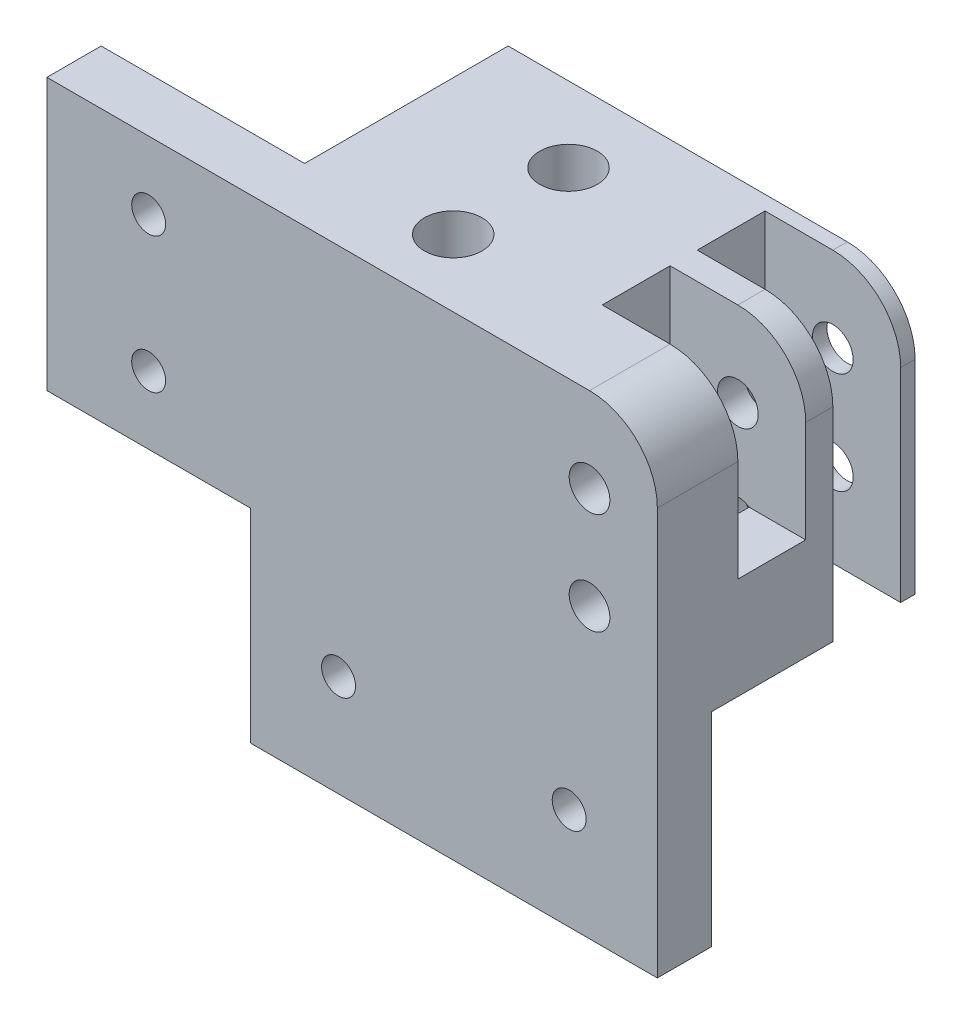
SolidWorks part; units mm, degrees
ref_plane "Front Plane" through (0, 0, 0) normal (0, 0, 1) x (1, 0, 0)
ref_plane "Top Plane" through (0, 0, 0) normal (0, 1, 0) x (1, 0, 0)
ref_plane "Right Plane" through (0, 0, 0) normal (1, 0, 0) x (0, 0, -1)
sketch "Esboço1" plane through (0, 0, 0) normal (0, 0, 1) x (1, 0, 0)
  line L0 (440, 72.2122) -> (440, 102.2122) construction
  line L1 (440, 72.2122) -> (380, 72.2122)
  line L2 (470, 102.2122) -> (470, 142.2122)
  line L3 (470, 142.2122) -> (390, 142.2122)
  line L4 (380, 72.2122) -> (380, 132.2122)
  line L5 (440, 102.2122) -> (470, 102.2122) construction
  line L6 (440, 72.2122) -> (440, 102.2122)
  line L7 (440, 102.2122) -> (470, 102.2122)
  line L9 (440, 87.2122) -> (380, 87.2122) construction
  line L10 (455, 102.2122) -> (455, 142.2122) construction
  arc A0 (390, 142.2122) -> (380, 132.2122) centre (390, 132.2122) ccw
  dimension "D1" = 10
  dimension "D2" = 40
  dimension "D3" = 60
extrude "Ressalto-extrusão1" add sketch "Esboço1" along normal blind 8 contours L4 A0 L3 L2 L7 L6 L1
hole_wizard "Broca de rosquear para tarraxa de M6x1.01" positions "Esboço2" profile "Esboço3" hole size "M6x1.0" standard "Ansi Metric" end condition through all
sketch "Esboço2" plane through (0, 0, 8) normal (0, 0, 1) x (1, 0, 0)
  line L0 (440, 87.2122) -> (380, 87.2122) construction
  line L1 (455, 102.2122) -> (455, 142.2122) construction
  line L2 (380, 72.2122) -> (380, 132.2122) construction
  line L3 (440, 72.2122) -> (440, 102.2122) construction
  line L4 (470, 142.2122) -> (390, 142.2122) construction
  point P0 (393, 87.2122)
  point P4 (427, 87.2122)
  point P6 (455, 112.2122)
  point P10 (455, 132.2122)
  dimension "D1" = 13
  dimension "D2" = 13
  dimension "D3" = 10
  dimension "D4" = 10
sketch "Esboço3" plane through (393, 87.2122, 8) normal (1, 0, 0) x (0, -1, 0)
  line L0 (0, 0) -> (0, 8)
  line L1 (0, 8) -> (2.5, 8)
  line L2 (2.5, 8) -> (2.5, 0)
  line L5 (2.5, 0) -> (0, 0)
  line L11 (0, -6.35) -> (0, 107.95) construction
  dimension "Thru Hole Dia." = 5
  dimension "Thru Hole Depth" = 8
sketch "Esboço4" plane through (0, 0, 0) normal (0, 0, -1) x (-1, 0, 0)
  line L0 (-470, 142.2122) -> (-390, 142.2122) construction
  line L1 (-390, 142.2122) -> (-440, 142.2122)
  line L2 (-380, 132.2122) -> (-380, 102.2122)
  line L3 (-380, 102.2122) -> (-440, 102.2122)
  line L4 (-440, 142.2122) -> (-440, 102.2122)
  line L5 (-380, 72.2122) -> (-380, 132.2122) construction
  arc A0 (-390, 142.2122) -> (-380, 132.2122) centre (-390, 132.2122) cw
  point P11 (-380, 142.2122)
  dimension "D1" = 10
extrude "Ressalto-extrusão2" add sketch "Esboço4" along normal blind 30
sketch "Esboço6" plane through (380, 0, 0) normal (-1, 0, 0) x (0, 0, 1)
  line L0 (-30, 142.2122) -> (0, 142.2122) construction
  line L1 (-27.8749, 102.2122) -> (-17.8749, 102.2122)
  line L2 (-27.8749, 102.2122) -> (-27.8749, 142.2122)
  line L3 (-27.8749, 142.2122) -> (-17.8749, 142.2122)
  line L4 (-17.8749, 102.2122) -> (-17.8749, 142.2122)
  line L5 (-13.8749, 117.2122) -> (-3.8749, 117.2122)
  line L6 (-13.8749, 117.2122) -> (-13.8749, 142.2122)
  line L7 (-13.8749, 142.2122) -> (-3.8749, 142.2122)
  line L8 (-3.8749, 117.2122) -> (-3.8749, 142.2122)
  dimension "D1" = 10
  dimension "D2" = 10
  dimension "D3" = 25
  dimension "D4" = 40
  dimension "D5" = 4
extrude "Corte-extrusão2" cut sketch "Esboço6" against normal blind 20
sketch "Esboço14" plane through (0, 0, -30) normal (0, 0, -1) x (-1, 0, 0)
  circle A2 centre (-390, 129.7122) radius 3
  circle A3 centre (-390, 129.7122) radius 3
  circle A5 centre (-390, 114.7122) radius 3
  circle A6 centre (-390, 114.7122) radius 3
  dimension "D1" = 0.5
  dimension "D2" = 0.5
extrude "Corte-extrusão6" cut sketch "Esboço14" against normal through all
sketch "Esboço15" plane through (0, 142.2122, 0) normal (0, 1, 0) x (1, 0, 0)
  circle A2 centre (420, 18.9024) radius 4.25
  circle A3 centre (420, 18.9024) radius 4.25
  circle A5 centre (420, 1.9024) radius 4.25
  circle A6 centre (420, 1.9024) radius 4.25
  dimension "D1" = 0
  dimension "D2" = 0
extrude "Corte-extrusão7" cut sketch "Esboço15" against normal up to surface (40 mm away) up to face at (400, 102.2122, -18.9374)
mirror "Espelhar1" about plane through (380, 72.2122, 8) normal (-1, 0, 0) of bodies 111
delete or keep bodies "Corpo-Excluir/Manter 1" type delete bodies bodies 111
